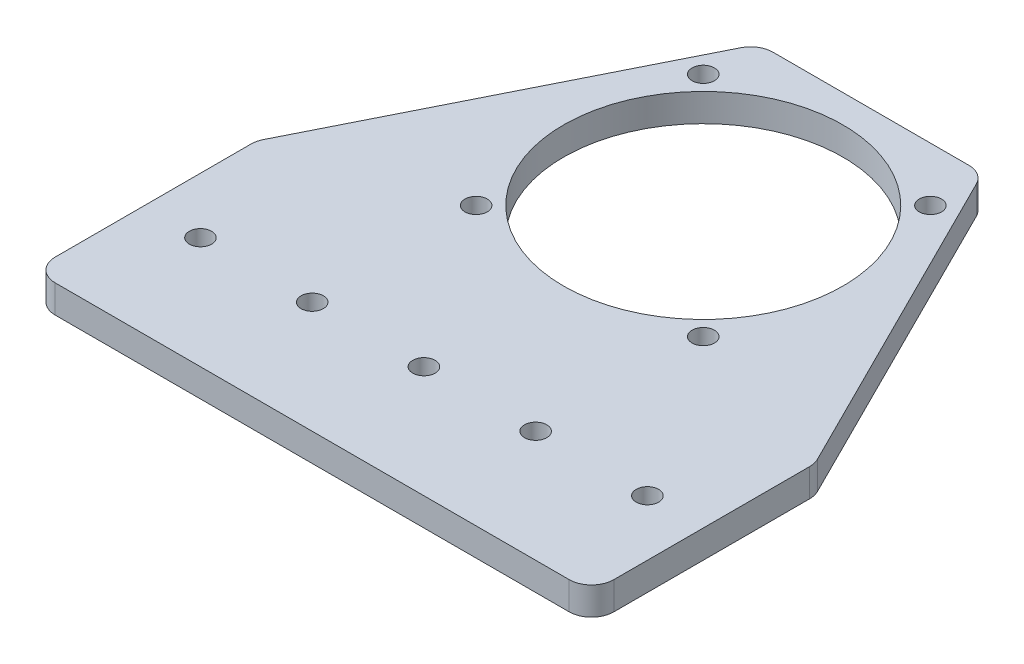
SolidWorks part; units mm, degrees
ref_plane "Front Plane" through (0, 0, 0) normal (0, 0, 1) x (1, 0, 0)
ref_plane "Top Plane" through (0, 0, 0) normal (0, 1, 0) x (1, 0, 0)
ref_plane "Right Plane" through (0, 0, 0) normal (1, 0, 0) x (0, 0, -1)
sketch "Sketch1" plane through (0, 0, 0) normal (0, 1, 0) x (1, 0, 0)
  line L0 (-31.75, -6.35) -> (31.75, -6.35) construction
  line L1 (-31.75, -31.75) -> (31.75, -31.75)
  line L2 (-31.75, -31.75) -> (-31.75, -6.35)
  line L3 (-12.7, 31.75) -> (12.7, 31.75)
  line L4 (31.75, -31.75) -> (31.75, -6.35)
  line L5 (-31.75, -31.75) -> (31.75, 31.75) construction
  line L6 (-31.75, 31.75) -> (31.75, -31.75) construction
  line L7 (-31.75, -6.35) -> (-12.7, 31.75)
  line L8 (31.75, -6.35) -> (12.7, 31.75)
  line L9 (-31.75, -6.35) -> (-31.75, 31.75) construction
  line L10 (-31.75, 31.75) -> (-12.7, 31.75) construction
  line L11 (12.7, 31.75) -> (31.75, 31.75) construction
  line L12 (31.75, 31.75) -> (31.75, -6.35) construction
  line L13 (0, 31.75) -> (0, -6.35) construction
  line L14 (-31.75, 12.7) -> (31.75, 12.7) construction
  line L15 (-12.9091, -0.2091) -> (12.9091, 25.6091)
  line L16 (-12.9091, 25.6091) -> (12.9091, -0.2091)
  line L17 (-31.75, -19.05) -> (31.75, -19.05) construction
  circle A0 centre (0, 12.7) radius 15.875
  circle A1 centre (12.9091, 25.6091) radius 1.27
  circle A2 centre (12.9091, -0.2091) radius 1.27
  circle A3 centre (-12.9091, -0.2091) radius 1.27
  circle A4 centre (-12.9091, 25.6091) radius 1.27
  circle A5 centre (-25.4, -19.05) radius 1.27
  point P0 (0, 0)
  point P19 (0, 12.7)
  point P22 (0, 12.7)
  dimension "D5" = 31.75
  dimension "D8" = 2.54
  dimension "D9" = 12.7
  dimension "D10" = 6.35
  dimension "D11" = 2.54
  dimension "D1" = 63.5
  dimension "D2" = 25.4
  dimension "D3" = 25.4
  dimension "D4" = 63.5
  dimension "D6" = 45
  dimension "D7" = 36.5125
extrude "Initial Bracket" add sketch "Sketch1" along normal blind 3.175 contours L4 L8 L3 L7 L2 L1 A4 A0 A1 A2 A3 region at (0.0517, 0, 9.658)
fillet "Edge Fillet" radius 2.54 6 edges at (-31.75, 1.5875, 6.35) (-31.75, 1.5875, 31.75) (31.75, 1.5875, 31.75) (31.75, 1.5875, 6.35) (12.7, 1.5875, -31.75) (-12.7, 1.5875, -31.75)
pattern_linear "LPattern1" count 5 spacing 12.7 along (1, 0, 0) of face at (-25.4, 3.175, 20.32)
